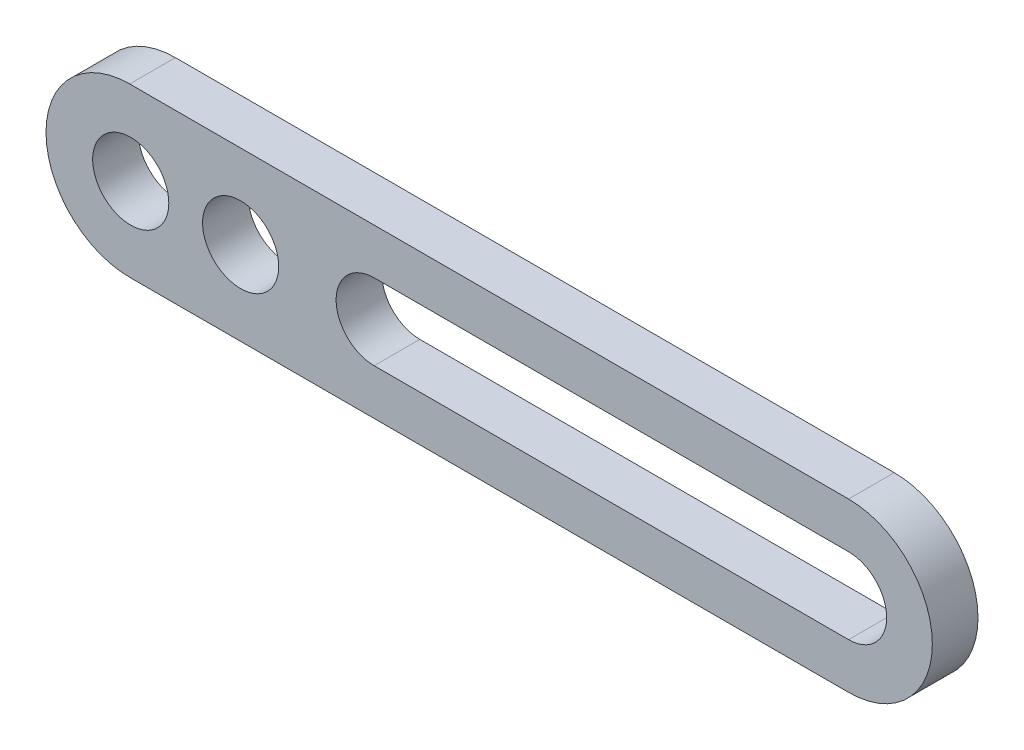
SolidWorks part; units mm, degrees
ref_plane "Front Plane" through (0, 0, 0) normal (0, 0, 1) x (1, 0, 0)
ref_plane "Top Plane" through (0, 0, 0) normal (0, 1, 0) x (1, 0, 0)
ref_plane "Right Plane" through (0, 0, 0) normal (1, 0, 0) x (0, 0, -1)
sketch "Sketch2" plane through (0, 0, 0) normal (0, 0, 1) x (1, 0, 0)
  line L0 (0, 0.7511) -> (54.3236, 0.7511) construction
  line L1 (15.9896, 3.2511) -> (47.1525, 3.2511)
  line L2 (15.9896, -1.7489) -> (47.1525, -1.7489)
  line L3 (-0.0651, 6.2511) -> (47.1525, 6.2511)
  line L4 (-0.0651, -4.7489) -> (47.1525, -4.7489)
  line L5 (-0.0651, 3.2511) -> (47.1525, 3.2511) construction
  line L6 (-0.0651, -1.7489) -> (47.1525, -1.7489) construction
  line L7 (13.4896, 0.7511) -> (47.1525, 0.7511) construction
  arc A1 (47.1525, -1.7489) -> (47.1525, 3.2511) centre (47.1525, 0.7511) ccw
  arc A2 (47.1525, -4.7489) -> (47.1525, 6.2511) centre (47.1525, 0.7511) ccw
  arc A3 (-0.0651, 6.2511) -> (-0.0651, -4.7489) centre (-0.0651, 0.7511) ccw
  circle A4 centre (0, 0.7511) radius 2.5
  circle A5 centre (7.2191, 0.7511) radius 2.5
  arc A6 (15.9896, 3.2511) -> (15.9896, -1.7489) centre (15.9896, 0.7511) ccw
  arc A7 (-0.0651, 3.2511) -> (-0.0651, -1.7489) centre (-0.0651, 0.7511) ccw construction
  point P3 (25, 0)
  point P18 (47.1525, -1.7489)
  point P22 (7.2191, 0.7511)
  dimension "D1" = 3
extrude "Boss-Extrude1" add sketch "Sketch2" along normal blind 3
